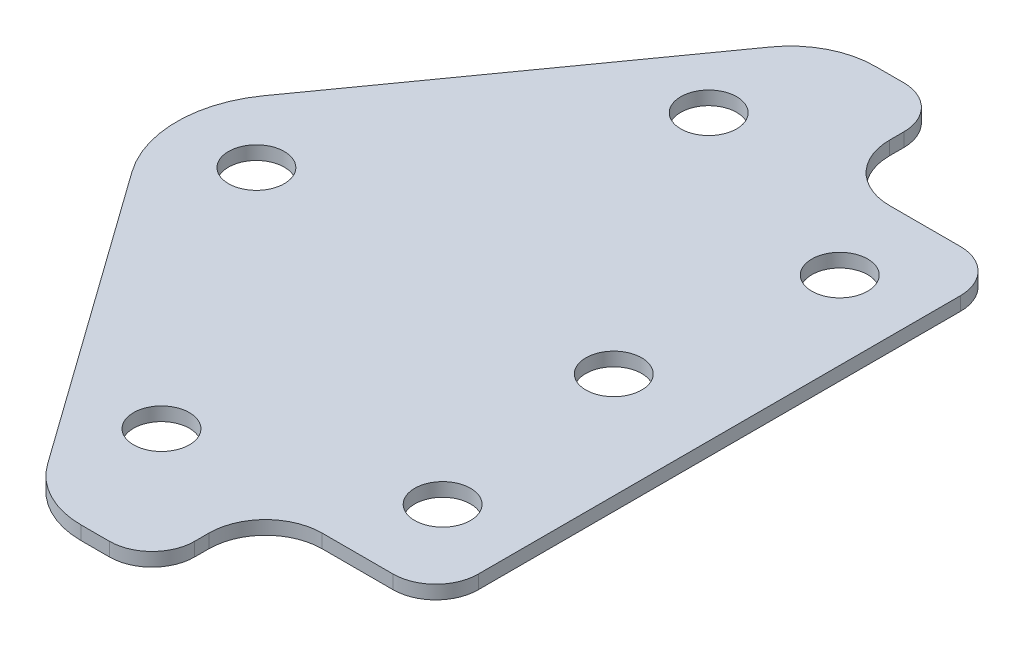
SolidWorks part; units mm, degrees
ref_plane "Front Plane" through (0, 0, 0) normal (0, 0, 1) x (1, 0, 0)
ref_plane "Top Plane" through (0, 0, 0) normal (0, 1, 0) x (1, 0, 0)
ref_plane "Right Plane" through (0, 0, 0) normal (1, 0, 0) x (0, 0, -1)
sketch "Sketch1" plane through (0, 0, 0) normal (0, 1, 0) x (1, 0, 0)
  line L0 (-63.7792, -177.8) -> (-190.7792, 0)
  line L5 (63.7792, -177.8) -> (-63.7792, -177.8)
  line L6 (63.7792, -177.8) -> (63.7792, 177.8)
  line L7 (63.7792, 177.8) -> (-63.7792, 177.8)
  line L9 (63.7792, -177.8) -> (-63.7792, 177.8) construction
  line L10 (63.7792, 177.8) -> (-63.7792, -177.8) construction
  line L11 (-190.7792, 0) -> (-63.7792, 177.8)
  point P0 (0, 0)
  dimension "D1" = 355.6
  dimension "D2" = 190.7792
  dimension "D3" = 127.5584
extrude "Boss-Extrude1" add sketch "Sketch1" along normal blind 6.096
sketch "Sketch3" plane through (0, 6.096, 0) normal (0, 1, 0) x (1, 0, 0)
  circle A4 centre (-143.5, 0) radius 12.5 construction
  circle A5 centre (16.5, 0) radius 12.5 construction
  circle A6 centre (-143.5, 0) radius 12.5
  circle A7 centre (16.5, 0) radius 12.5
extrude "vertical holes" cut sketch "Sketch3" against normal blind 44.45
sketch "Sketch4" plane through (0, 0, 0) normal (0, -1, 0) x (1, 0, 0)
  line L0 (-63.5, 122.5) -> (-63.5, 0) construction
  line L1 (-63.5, 0) -> (0, 0) construction
  line L2 (-63.5, 0) -> (-63.5, -122.5) construction
  line L3 (63.7792, 177.8) -> (63.7792, -177.8) construction
  circle A2 centre (-63.5, 122.5) radius 12.5
  circle A3 centre (-63.5, -122.5) radius 12.5
  point P11 (63.7792, 0)
  dimension "D2" = 25
  dimension "D1" = 122.5
  dimension "D3" = 63.5
  dimension "D4" = 63.5
extrude "horizontal holes" cut sketch "Sketch4" against normal up to surface (6.096 mm away) up to face at (-143.5, 6.096, 12.5)
sketch "Sketch5" plane through (0, 0, 0) normal (0, -1, 0) x (1, 0, 0)
  line L0 (28.7792, 88.9) -> (16.5, 88.9) construction
  line L1 (63.7792, 177.8) -> (63.7792, -177.8) construction
  line L2 (-63.5, -88.9) -> (63.7792, -88.9) construction
  line L3 (16.5, 0) -> (16.5, 88.9) construction
  line L4 (16.5, 0) -> (16.5, -88.9) construction
  line L5 (28.7792, 88.9) -> (28.7792, -88.9) construction
  circle A0 centre (28.7792, 88.9) radius 12.5
  circle A1 centre (28.7792, -88.9) radius 12.5
  circle A2 centre (-63.5, -122.5) radius 12.5 construction
  circle A3 centre (-63.5, 122.5) radius 12.5 construction
  circle A4 centre (-63.5, 122.5) radius 12.5 construction
  circle A5 centre (16.5, 0) radius 12.5 construction
  circle A6 centre (16.5, 0) radius 12.5 construction
  dimension "D1" = 35
  dimension "D2" = 88.9
extrude "upper support" cut sketch "Sketch5" against normal through all contours A1 | A0 region at (28.7792, 0, -88.9)
sketch "Sketch6" plane through (0, 0, 0) normal (0, -1, 0) x (1, 0, 0)
  line L10 (-63.7792, 177.8) -> (63.7792, 177.8) construction
  line L12 (63.7792, -177.8) -> (-12.4208, -177.8)
  line L13 (63.7792, -177.8) -> (63.7792, -127)
  line L14 (63.7792, -127) -> (-12.4208, -127)
  line L15 (-12.4208, -177.8) -> (-12.4208, -127)
  line L16 (63.7792, 177.8) -> (-12.4208, 177.8)
  line L17 (63.7792, 177.8) -> (63.7792, 127)
  line L18 (63.7792, 127) -> (-12.4208, 127)
  line L19 (-12.4208, 177.8) -> (-12.4208, 127)
  line L20 (63.7792, 177.8) -> (63.7792, -177.8) construction
  line L21 (63.7792, -177.8) -> (-63.7792, -177.8) construction
  dimension "D1" = 76.2
  dimension "D2" = 50.8
extrude "Cut-Extrude2" cut sketch "Sketch6" against normal through all
fillet "Fillet1" radius 25.4 2 edges at (-12.4208, 3.048, -127) (-12.4208, 3.048, 127)
fillet "Fillet2" radius 19.05 4 edges at (63.7792, 3.048, 127) (63.7792, 3.048, -127) (-12.4208, 3.048, -177.8) (-12.4208, 3.048, 177.8)
fillet "Fillet3" radius 38.1 2 edges at (-63.7792, 3.048, -177.8) (-63.7792, 3.048, 177.8)
fillet "Fillet4" radius 50.8 1 edges at (-190.7792, 3.048, 0)
